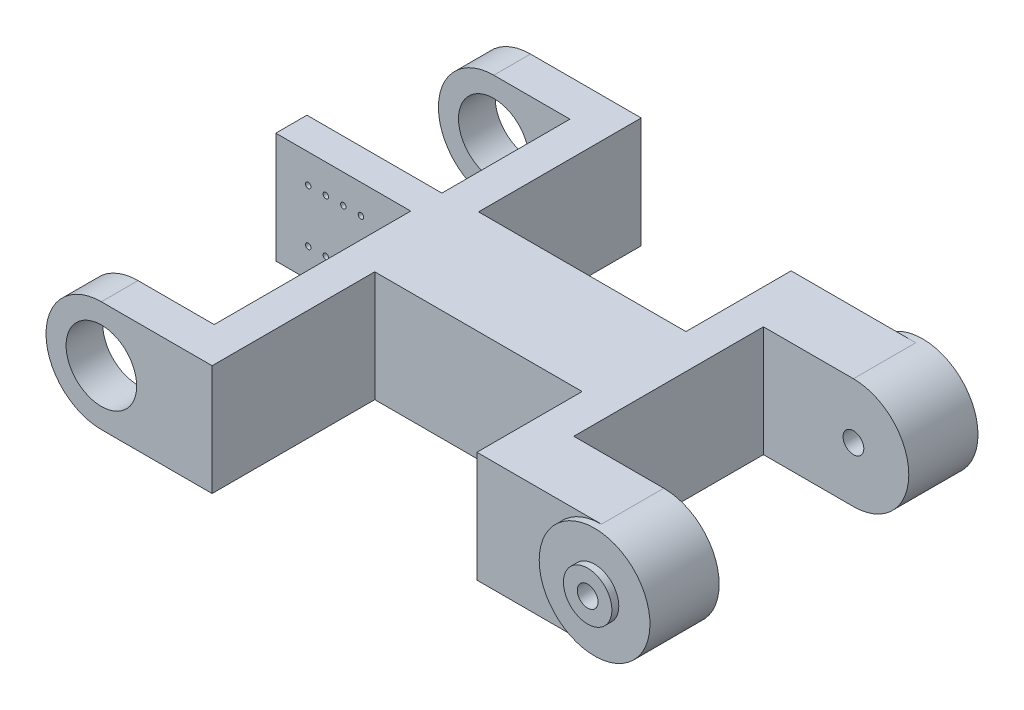
SolidWorks part; units mm, degrees
ref_plane "Front Plane" through (0, 0, 0) normal (0, 0, 1) x (1, 0, 0)
ref_plane "Top Plane" through (0, 0, 0) normal (0, 1, 0) x (1, 0, 0)
ref_plane "Right Plane" through (0, 0, 0) normal (1, 0, 0) x (0, 0, -1)
sketch "Sketch1" plane through (0, 0, 0) normal (0, 0, 1) x (1, 0, 0)
  circle A0 centre (-20.525, 142.3) radius 3.5
  circle A1 centre (-20.525, 57.87) radius 3.5 construction
  circle A2 centre (-20.525, 142.3) radius 1.5 construction
  circle A3 centre (-20.525, 142.3) radius 1.5
extrude "Boss-Extrude1" add sketch "Sketch1" along normal up to surface (1 mm away)
sketch "Sketch2" plane through (0, 0, 1) normal (0, 0, 1) x (1, 0, 0)
  circle A0 centre (-20.525, 142.3) radius 1.5 construction
  circle A1 centre (-20.525, 142.3) radius 1.5
  circle A2 centre (-20.525, 142.3) radius 8
  circle A3 centre (-20.525, 57.87) radius 8 construction
extrude "Boss-Extrude2" add sketch "Sketch2" along normal up to surface (10 mm away)
sketch "Sketch3" plane through (0, 0, 49.4) normal (0, 0, -1) x (-1, 0, 0)
  circle A1 centre (20.525, 142.3) radius 1.5
  circle A2 centre (20.525, 142.3) radius 1.5
  circle A3 centre (20.525, 142.3) radius 3.5
  circle A4 centre (20.525, 142.3) radius 3.5
  dimension "D1" = 0
  dimension "D2" = 0
extrude "Boss-Extrude4" add sketch "Sketch3" along normal up to surface (1 mm away) separate body contours A4 A2 region at (-17.124, 142.3, 49.4)
sketch "Sketch4" plane through (0, 0, 48.4) normal (0, 0, -1) x (-1, 0, 0)
  circle A0 centre (20.525, 142.3) radius 8 construction
  circle A1 centre (20.525, 142.3) radius 8
  circle A2 centre (20.525, 142.3) radius 1.5 construction
  circle A3 centre (20.525, 142.3) radius 1.5
extrude "Boss-Extrude5" add sketch "Sketch4" along normal up to surface (10 mm away)
sketch "Sketch5" plane through (0, 0, -6.3) normal (0, 0, -1) x (-1, 0, 0)
  circle A0 centre (84.485, 142.3) radius 8
  circle A1 centre (84.485, 142.3) radius 5.1
  circle A2 centre (20.525, 142.3) radius 5.1 construction
  dimension "D1" = 16
extrude "Boss-Extrude6" add sketch "Sketch5" against normal up to surface (5.3 mm away) separate body
sketch "Sketch6" plane through (0, 0, 55.7) normal (0, 0, 1) x (1, 0, 0)
  circle A1 centre (-84.485, 142.3) radius 5.1
  circle A2 centre (-84.485, 142.3) radius 5.1
  circle A3 centre (-84.485, 142.3) radius 8
  circle A4 centre (-84.485, 142.3) radius 8
  dimension "D1" = 0
  dimension "D2" = 0
extrude "Boss-Extrude7" add sketch "Sketch6" against normal up to surface (5.3 mm away) separate body
sketch "Sketch7" plane through (0, 0, 55.7) normal (0, 0, 1) x (1, 0, 0)
  line L0 (-84.485, 150.3) -> (-73.485, 150.3)
  line L1 (-84.485, 142.3) -> (-84.485, 196.4876) construction
  line L2 (-73.485, 150.3) -> (-73.485, 134.3)
  line L3 (-73.485, 134.3) -> (-84.485, 134.3)
  circle A0 centre (-84.485, 142.3) radius 8 construction
  circle A1 centre (-84.485, 142.3) radius 8
  circle M4 centre (-84.485, 142.3) radius 8
  dimension "D1" = 3
extrude "Boss-Extrude8" add sketch "Sketch7" against normal up to surface (5.3 mm away) contours L3 L2 L0 M4 region at (-76.1814, 142.3, 55.7) up to face at (-92.485, 142.3, 50.4)
sketch "Sketch8" plane through (0, 0, -1) normal (0, 0, 1) x (1, 0, 0)
  line L0 (-84.485, 150.3) -> (-73.485, 150.3) construction
  line L1 (-73.485, 150.3) -> (-73.485, 134.3) construction
  line L2 (-73.485, 134.3) -> (-84.485, 134.3) construction
  line L3 (-84.485, 150.3) -> (-73.485, 150.3)
  line L4 (-73.485, 150.3) -> (-73.485, 134.3)
  line L5 (-73.485, 134.3) -> (-84.485, 134.3)
  circle A1 centre (-84.485, 142.3) radius 8
  circle A2 centre (-84.485, 142.3) radius 8
  circle M2 centre (-84.485, 142.3) radius 8
  dimension "D1" = 0
extrude "Boss-Extrude9" add sketch "Sketch8" against normal up to surface (5.3 mm away) contours L5 L4 L3 M2 region at (-76.1814, 142.3, -1) up to face at (-84.485, 147.4, -6.3)
sketch "Sketch9" plane through (0, 0, 11) normal (0, 0, 1) x (1, 0, 0)
  line L0 (-20.525, 150.3) -> (-33.525, 150.3)
  line L1 (-33.525, 150.3) -> (-33.525, 134.3)
  line L2 (-33.525, 134.3) -> (-20.525, 134.3)
  circle A0 centre (-20.525, 142.3) radius 8 construction
  circle A1 centre (-20.525, 142.3) radius 8
  circle M5 centre (-20.525, 142.3) radius 8
  dimension "D1" = 5
extrude "Boss-Extrude10" add sketch "Sketch9" against normal offset from surface (9 mm away) 1 contours L1 L2 L0 M5 region at (-29.9293, 142.3, 11) up to face at (-24.025, 142.3, 1)
sketch "Sketch10" plane through (0, 0, 38.4) normal (0, 0, -1) x (-1, 0, 0)
  line L0 (20.525, 150.3) -> (33.525, 150.3) construction
  line L1 (33.525, 150.3) -> (33.525, 134.3) construction
  line L2 (33.525, 134.3) -> (20.525, 134.3) construction
  line L3 (20.525, 150.3) -> (33.525, 150.3)
  line L4 (33.525, 150.3) -> (33.525, 134.3)
  line L5 (33.525, 134.3) -> (20.525, 134.3)
  circle A1 centre (20.525, 142.3) radius 8
  circle A2 centre (20.525, 142.3) radius 8
  circle M3 centre (20.525, 142.3) radius 8
  dimension "D1" = 0
extrude "Boss-Extrude11" add sketch "Sketch10" against normal offset from surface (9 mm away) 1 contours L5 L4 L3 M3 region at (-29.9293, 142.3, 38.4) up to face at (-17.025, 142.3, 48.4)
sketch "Sketch11" plane through (-33.525, 0, 0) normal (-1, 0, 0) x (0, 0, 1)
  line L1 (2, 150.3) -> (47.4, 150.3)
  line L2 (2, 150.3) -> (2, 134.3)
  line L3 (2, 134.3) -> (47.4, 134.3)
  line L4 (47.4, 150.3) -> (47.4, 134.3)
extrude "Boss-Extrude12" add sketch "Sketch11" along normal blind 5
sketch "Sketch12" plane through (-73.485, 0, 0) normal (1, 0, 0) x (0, 0, -1)
  line L1 (-55.7, 150.3) -> (6.3, 150.3)
  line L2 (-55.7, 150.3) -> (-55.7, 134.3)
  line L3 (-55.7, 134.3) -> (6.3, 134.3)
  line L4 (6.3, 150.3) -> (6.3, 134.3)
extrude "Boss-Extrude13" add sketch "Sketch12" along normal blind 5
sketch "Sketch13" plane through (-38.525, 0, 0) normal (-1, 0, 0) x (0, 0, 1)
  line L0 (-6.3, 142.3) -> (55.7, 142.3) construction
  line L1 (-6.3, 150.3) -> (-6.3, 134.3) construction
  line L2 (55.7, 134.3) -> (55.7, 150.3) construction
  line L3 (-1, 150.3) -> (50.4, 150.3) construction
  line L4 (17.2, 134.3) -> (32.2, 134.3)
  line L5 (17.2, 134.3) -> (17.2, 150.3)
  line L6 (17.2, 150.3) -> (32.2, 150.3)
  line L7 (32.2, 134.3) -> (32.2, 150.3)
  line L8 (17.2, 134.3) -> (32.2, 150.3) construction
  line L9 (17.2, 150.3) -> (32.2, 134.3) construction
  point P6 (24.7, 142.3)
  dimension "D1" = 15
extrude "Boss-Extrude14" add sketch "Sketch13" along normal up to surface (29.96 mm away) up to face at (-68.485, 142.3, 24.7)
sketch "Sketch14" plane through (0, 0, 20) normal (0, 0, 1) x (1, 0, 0)
  line L0 (-92.985, 134.3) -> (-75.985, 134.3)
  line L1 (-75.985, 134.3) -> (-75.985, 150.3)
  line L2 (-75.985, 150.3) -> (-92.985, 150.3)
  line L3 (-92.985, 150.3) -> (-92.985, 134.3)
  line L4 (-78.485, 147.8) -> (-90.485, 147.8)
  line L5 (-90.485, 147.8) -> (-90.485, 136.8)
  line L6 (-90.485, 136.8) -> (-78.485, 136.8)
  line L7 (-78.485, 136.8) -> (-78.485, 147.8)
  line L8 (-78.485, 147.8) -> (-90.485, 147.8)
  line L9 (-90.485, 147.8) -> (-90.485, 136.8)
  line L10 (-90.485, 136.8) -> (-78.485, 136.8)
  line L11 (-78.485, 136.8) -> (-78.485, 147.8)
  line L12 (-73.485, 150.3) -> (-73.485, 134.3) construction
  line L13 (-73.485, 150.3) -> (-73.485, 134.3)
  line L14 (-73.485, 150.3) -> (-75.985, 150.3)
  line L15 (-73.485, 134.3) -> (-75.985, 134.3)
  circle M11 centre (-88.295, 146.11) radius 0.4
  circle M12 centre (-80.675, 138.49) radius 0.4
  circle M13 centre (-83.215, 138.49) radius 0.4
  circle M14 centre (-85.755, 138.49) radius 0.4
  circle M15 centre (-85.755, 146.11) radius 0.4
  circle M16 centre (-83.215, 146.11) radius 0.4
  circle M17 centre (-80.675, 146.11) radius 0.4
  circle M18 centre (-88.295, 138.49) radius 0.4
  line M19 (-78.485, 147.8) -> (-90.485, 147.8)
  line M20 (-90.485, 147.8) -> (-90.485, 136.8)
  line M21 (-90.485, 136.8) -> (-78.485, 136.8)
  line M22 (-78.485, 136.8) -> (-78.485, 147.8)
  dimension "D1" = 0
  dimension "D2" = 2.5
extrude "Boss-Extrude15" add sketch "Sketch14" along normal up to surface (2 mm away) contours L2 L3 L0 L1 M19 M22 M21 M20 | M22 M19 M20 M21 M12 M14 M16 M18 M17 M15 M13 M11 | L15 L13 L14 L1 region at (-92.7515, 142.3, 20) region at (-74.735, 142.3, 20) region at (-84.485, 142.3, 20)
sketch "Sketch15" plane through (0, 0, 20) normal (0, 0, -1) x (-1, 0, 0)
  line L4 (90.485, 147.8) -> (78.485, 147.8)
  line L5 (78.485, 147.8) -> (78.485, 136.8)
  line L6 (78.485, 136.8) -> (90.485, 136.8)
  line L7 (90.485, 136.8) -> (90.485, 147.8)
  line L8 (90.485, 147.8) -> (78.485, 147.8)
  line L9 (78.485, 147.8) -> (78.485, 136.8)
  line L10 (78.485, 136.8) -> (90.485, 136.8)
  line L11 (90.485, 136.8) -> (90.485, 147.8)
  line L12 (92.985, 150.3) -> (73.485, 150.3)
  line L13 (73.485, 150.3) -> (73.485, 134.3)
  line L14 (73.485, 134.3) -> (92.985, 134.3)
  line L15 (92.985, 134.3) -> (92.985, 150.3)
  line L16 (92.985, 150.3) -> (73.485, 150.3)
  line L17 (73.485, 150.3) -> (73.485, 134.3)
  line L18 (73.485, 134.3) -> (92.985, 134.3)
  line L19 (92.985, 134.3) -> (92.985, 150.3)
  dimension "D1" = 0
  dimension "D2" = 0
extrude "Boss-Extrude16" add sketch "Sketch15" along normal up to surface (2.5 mm away)
